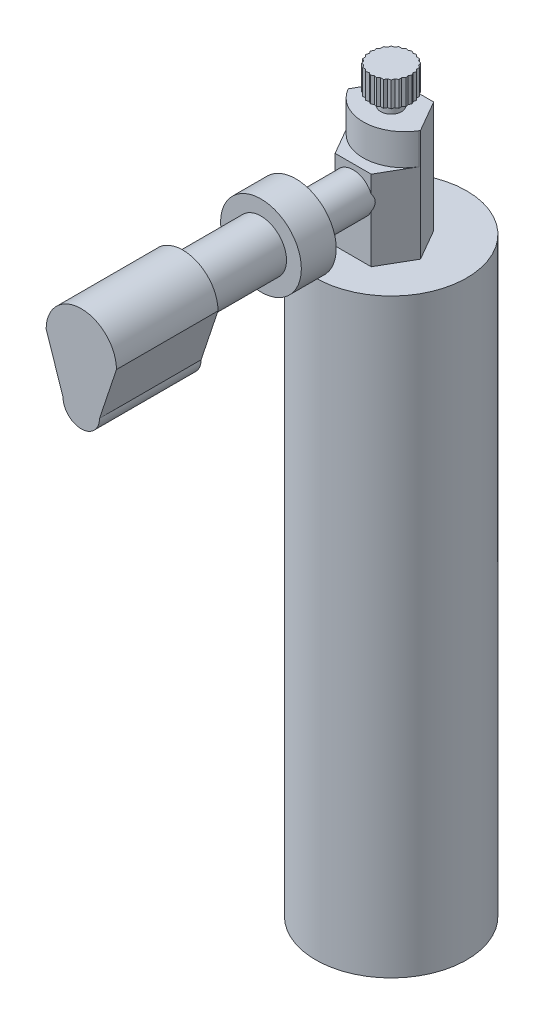
SolidWorks part; units mm, degrees
ref_plane "Front Plane" through (0, 0, 0) normal (0, 0, 1) x (1, 0, 0)
ref_plane "Top Plane" through (0, 0, 0) normal (0, 1, 0) x (1, 0, 0)
ref_plane "Right Plane" through (0, 0, 0) normal (1, 0, 0) x (0, 0, -1)
sketch "Sketch1" plane through (0, 0, 0) normal (0, 1, 0) x (1, 0, 0)
  circle A0 centre (0, 0) radius 14.5
  dimension "D1" = 29
extrude "Boss-Extrude1" add sketch "Sketch1" along normal blind 113.4
sketch "Sketch2" plane through (0, 113.4, 0) normal (0, 1, 0) x (1, 0, 0)
  circle A0 centre (0, 0) radius 2
  dimension "D1" = 4
extrude "Boss-Extrude2" add sketch "Sketch2" along normal blind 28.5
sketch "Sketch3" plane through (0, 141.9, 0) normal (0, 1, 0) x (1, 0, 0)
  circle A0 centre (0, 0) radius 4
  dimension "D1" = 8
extrude "Boss-Extrude3" add sketch "Sketch3" against normal blind 4.8
sketch "Sketch4" plane through (0, 113.4, 0) normal (0, 1, 0) x (1, 0, 0)
  line L3 (3.4641, 4.7) -> (-3.4641, 4.7)
  line L4 (-3.4641, 4.7) -> (-6.9282, -1.3)
  line L5 (-6.9282, -1.3) -> (-3.4641, -7.3)
  line L6 (-3.4641, -7.3) -> (3.4641, -7.3)
  line L7 (3.4641, -7.3) -> (6.9282, -1.3)
  line L8 (6.9282, -1.3) -> (3.4641, 4.7)
  circle A0 centre (0, 0) radius 14.5 construction
  circle A1 centre (0, -1.3) radius 6.9282 construction
  circle A4 centre (0, 0) radius 14.5 construction
  dimension "D1" = 12
  dimension "D2" = 4.7
extrude "Boss-Extrude4" add sketch "Sketch4" along normal blind 21.4
sketch "Sketch6" plane through (0, 134.8, 0) normal (0, 1, 0) x (1, 0, 0)
  line L4 (-6.9282, -1.3) -> (-6.9282, -9.4658)
  line L5 (-6.9282, -9.4658) -> (6.9282, -9.4658)
  line L6 (6.9282, -1.3) -> (6.9282, -9.4658)
  arc A0 (-6.9282, -1.3) -> (6.9282, -1.3) centre (0, 2.5618) ccw
extrude "Cut-Extrude1" cut sketch "Sketch6" against normal blind 6
sketch "Sketch7" plane through (0, 0, 7.3) normal (0, 0, 1) x (1, 0, 0)
  line L0 (-3.4641, 128.8) -> (3.4641, 128.8) construction
  circle A0 centre (0, 124.05) radius 3.75
  dimension "D1" = 7.5
  dimension "D2" = 4.75
extrude "Boss-Extrude5" add sketch "Sketch7" along normal blind 11 and the other way blind 2
sketch "Sketch8" plane through (0, 0, 18.3) normal (0, 0, 1) x (1, 0, 0)
  circle A0 centre (0, 124.05) radius 7.75
  dimension "D1" = 15.5
extrude "Boss-Extrude6" add sketch "Sketch8" along normal blind 6.7
sketch "Sketch9" plane through (0, 0, 25) normal (0, 0, 1) x (1, 0, 0)
  circle A0 centre (0, 124.05) radius 4.9
  dimension "D1" = 9.8
extrude "Boss-Extrude7" add sketch "Sketch9" along normal blind 15
sketch "Sketch10" plane through (0, 0, 40) normal (0, 0, 1) x (1, 0, 0)
  line L0 (0, 117.8) -> (0, 110.8) construction
  line L1 (-6.75, 124.05) -> (-3.5, 114.3)
  line L2 (3.5, 114.3) -> (6.75, 124.05)
  arc A0 (6.75, 124.05) -> (-6.75, 124.05) centre (0, 124.05) ccw
  arc A1 (-3.5, 114.3) -> (3.5, 114.3) centre (0, 114.3) ccw
  dimension "D1" = 13.5
  dimension "D2" = 7
extrude "Boss-Extrude8" add sketch "Sketch10" along normal blind 19.5
sketch "Sketch11" plane through (0, 141.9, 0) normal (0, 1, 0) x (1, 0, 0)
  line L0 (0, 4) -> (0.2732, 3.6147)
  line L1 (0, 4) -> (0, 3.625) construction
  line L2 (0, 4) -> (-0.2732, 3.6147)
  line L3 (0.6106, 3.9531) -> (0.8217, 3.5306)
  line L4 (0.6106, 3.9531) -> (0.2818, 3.614)
  line L5 (1.2069, 3.8136) -> (1.351, 3.3638)
  line L6 (1.2069, 3.8136) -> (0.8302, 3.5287)
  line L7 (1.7749, 3.5847) -> (1.8487, 3.1182)
  line L8 (1.7749, 3.5847) -> (1.3591, 3.3606)
  line L9 (2.3013, 3.2717) -> (2.303, 2.7994)
  line L10 (2.3013, 3.2717) -> (1.8562, 3.1137)
  line L11 (2.7737, 2.8821) -> (2.7034, 2.4151)
  line L12 (2.7737, 2.8821) -> (2.3097, 2.7939)
  line L13 (3.1812, 2.4249) -> (3.0403, 1.9741)
  line L14 (3.1812, 2.4249) -> (2.7091, 2.4086)
  line L15 (3.514, 1.9109) -> (3.306, 1.4868)
  line L16 (3.514, 1.9109) -> (3.0451, 1.9668)
  line L17 (3.7646, 1.3521) -> (3.4943, 0.9648)
  line L18 (3.7646, 1.3521) -> (3.3096, 1.4789)
  line L19 (3.9268, 0.7616) -> (3.6006, 0.4201)
  line L20 (3.9268, 0.7616) -> (3.4966, 0.9564)
  line L21 (3.9971, 0.1532) -> (3.6225, -0.1345)
  line L22 (3.9971, 0.1532) -> (3.6016, 0.4114)
  line L23 (3.9736, -0.4587) -> (3.5595, -0.6859)
  line L24 (3.9736, -0.4587) -> (3.6222, -0.1432)
  line L25 (3.857, -1.0599) -> (3.4131, -1.2212)
  line L26 (3.857, -1.0599) -> (3.5579, -0.6944)
  line L27 (3.65, -1.6363) -> (3.1867, -1.7279)
  line L28 (3.65, -1.6363) -> (3.4102, -1.2294)
  line L29 (3.3575, -2.1743) -> (2.8856, -2.1941)
  line L30 (3.3575, -2.1743) -> (3.1825, -1.7356)
  line L31 (2.9862, -2.6613) -> (2.5168, -2.6089)
  line L32 (2.9862, -2.6613) -> (2.8803, -2.201)
  line L33 (2.545, -3.086) -> (2.0891, -2.9625)
  line L34 (2.545, -3.086) -> (2.5106, -2.6149)
  line L35 (2.0441, -3.4383) -> (1.6124, -3.2467)
  line L36 (2.0441, -3.4383) -> (2.082, -2.9675)
  line L37 (1.4953, -3.71) -> (1.0979, -3.4547)
  line L38 (1.4953, -3.71) -> (1.6046, -3.2505)
  line L39 (0.9114, -3.8948) -> (0.5577, -3.5818)
  line L40 (0.9114, -3.8948) -> (1.0896, -3.4574)
  line L41 (0.3062, -3.9883) -> (0.0044, -3.625)
  line L42 (0.3062, -3.9883) -> (0.5491, -3.5832)
  line L43 (-0.3062, -3.9883) -> (-0.5491, -3.5832)
  line L44 (-0.3062, -3.9883) -> (-0.0044, -3.625)
  line L45 (-0.9114, -3.8948) -> (-1.0896, -3.4574)
  line L46 (-0.9114, -3.8948) -> (-0.5577, -3.5818)
  line L47 (-1.4953, -3.71) -> (-1.6046, -3.2505)
  line L48 (-1.4953, -3.71) -> (-1.0979, -3.4547)
  line L49 (-2.0441, -3.4383) -> (-2.082, -2.9675)
  line L50 (-2.0441, -3.4383) -> (-1.6124, -3.2467)
  line L51 (-2.545, -3.086) -> (-2.5106, -2.6149)
  line L52 (-2.545, -3.086) -> (-2.0891, -2.9625)
  line L53 (-2.9862, -2.6613) -> (-2.8803, -2.201)
  line L54 (-2.9862, -2.6613) -> (-2.5168, -2.6089)
  line L55 (-3.3575, -2.1743) -> (-3.1825, -1.7356)
  line L56 (-3.3575, -2.1743) -> (-2.8856, -2.1941)
  line L57 (-3.65, -1.6363) -> (-3.4102, -1.2294)
  line L58 (-3.65, -1.6363) -> (-3.1867, -1.7279)
  line L59 (-3.857, -1.0599) -> (-3.5579, -0.6944)
  line L60 (-3.857, -1.0599) -> (-3.4131, -1.2212)
  line L61 (-3.9736, -0.4587) -> (-3.6222, -0.1432)
  line L62 (-3.9736, -0.4587) -> (-3.5595, -0.6859)
  line L63 (-3.9971, 0.1532) -> (-3.6016, 0.4114)
  line L64 (-3.9971, 0.1532) -> (-3.6225, -0.1345)
  line L65 (-3.9268, 0.7616) -> (-3.4966, 0.9564)
  line L66 (-3.9268, 0.7616) -> (-3.6006, 0.4201)
  line L67 (-3.7646, 1.3521) -> (-3.3096, 1.4789)
  line L68 (-3.7646, 1.3521) -> (-3.4943, 0.9648)
  line L69 (-3.514, 1.9109) -> (-3.0451, 1.9668)
  line L70 (-3.514, 1.9109) -> (-3.306, 1.4868)
  line L71 (-3.1812, 2.4249) -> (-2.7091, 2.4086)
  line L72 (-3.1812, 2.4249) -> (-3.0403, 1.9741)
  line L73 (-2.7737, 2.8821) -> (-2.3097, 2.7939)
  line L74 (-2.7737, 2.8821) -> (-2.7034, 2.4151)
  line L75 (-2.3013, 3.2717) -> (-1.8562, 3.1137)
  line L76 (-2.3013, 3.2717) -> (-2.303, 2.7994)
  line L77 (-1.7749, 3.5847) -> (-1.3591, 3.3606)
  line L78 (-1.7749, 3.5847) -> (-1.8487, 3.1182)
  line L79 (-1.2069, 3.8136) -> (-0.8302, 3.5287)
  line L80 (-1.2069, 3.8136) -> (-1.351, 3.3638)
  line L81 (-0.6106, 3.9531) -> (-0.2818, 3.614)
  line L82 (-0.6106, 3.9531) -> (-0.8217, 3.5306)
  arc A0 (-0.2732, 3.6147) -> (-0.2818, 3.614) centre (0, 0) ccw construction
  circle A1 centre (0, 0) radius 4 construction
  circle A2 centre (0, 0) radius 4
  arc A3 (0.2818, 3.614) -> (0.2732, 3.6147) centre (0, 0) ccw
  arc A4 (0.2818, 3.614) -> (0.2732, 3.6147) centre (0, 0) ccw construction
  arc A5 (0.8302, 3.5287) -> (0.8217, 3.5306) centre (0, 0) ccw construction
  arc A6 (0.8302, 3.5287) -> (0.8217, 3.5306) centre (0, 0) ccw
  arc A7 (1.3591, 3.3606) -> (1.351, 3.3638) centre (0, 0) ccw construction
  arc A8 (1.3591, 3.3606) -> (1.351, 3.3638) centre (0, 0) ccw
  arc A9 (-0.2732, 3.6147) -> (-0.2818, 3.614) centre (0, 0) ccw
  arc A10 (-0.8217, 3.5306) -> (-0.8302, 3.5287) centre (0, 0) ccw construction
  arc A11 (-0.8217, 3.5306) -> (-0.8302, 3.5287) centre (0, 0) ccw
  arc A12 (-1.351, 3.3638) -> (-1.3591, 3.3606) centre (0, 0) ccw construction
  arc A13 (-1.351, 3.3638) -> (-1.3591, 3.3606) centre (0, 0) ccw
  arc A14 (-1.8487, 3.1182) -> (-1.8562, 3.1137) centre (0, 0) ccw construction
  arc A15 (-1.8487, 3.1182) -> (-1.8562, 3.1137) centre (0, 0) ccw
  arc A16 (1.8562, 3.1137) -> (1.8487, 3.1182) centre (0, 0) ccw construction
  arc A17 (1.8562, 3.1137) -> (1.8487, 3.1182) centre (0, 0) ccw
  arc A18 (2.3097, 2.7939) -> (2.303, 2.7994) centre (0, 0) ccw construction
  arc A19 (2.3097, 2.7939) -> (2.303, 2.7994) centre (0, 0) ccw
  arc A20 (2.7091, 2.4086) -> (2.7034, 2.4151) centre (0, 0) ccw construction
  arc A21 (2.7091, 2.4086) -> (2.7034, 2.4151) centre (0, 0) ccw
  arc A22 (3.0451, 1.9668) -> (3.0403, 1.9741) centre (0, 0) ccw construction
  arc A23 (3.0451, 1.9668) -> (3.0403, 1.9741) centre (0, 0) ccw
  arc A24 (3.3096, 1.4789) -> (3.306, 1.4868) centre (0, 0) ccw construction
  arc A25 (3.3096, 1.4789) -> (3.306, 1.4868) centre (0, 0) ccw
  arc A26 (3.4966, 0.9564) -> (3.4943, 0.9648) centre (0, 0) ccw construction
  arc A27 (3.4966, 0.9564) -> (3.4943, 0.9648) centre (0, 0) ccw
  arc A28 (3.6016, 0.4114) -> (3.6006, 0.4201) centre (0, 0) ccw construction
  arc A29 (3.6016, 0.4114) -> (3.6006, 0.4201) centre (0, 0) ccw
  arc A30 (3.6222, -0.1432) -> (3.6225, -0.1345) centre (0, 0) ccw construction
  arc A31 (3.6222, -0.1432) -> (3.6225, -0.1345) centre (0, 0) ccw
  arc A32 (3.5579, -0.6944) -> (3.5595, -0.6859) centre (0, 0) ccw construction
  arc A33 (3.5579, -0.6944) -> (3.5595, -0.6859) centre (0, 0) ccw
  arc A34 (3.4102, -1.2294) -> (3.4131, -1.2212) centre (0, 0) ccw construction
  arc A35 (3.4102, -1.2294) -> (3.4131, -1.2212) centre (0, 0) ccw
  arc A36 (3.1825, -1.7356) -> (3.1867, -1.7279) centre (0, 0) ccw construction
  arc A37 (3.1825, -1.7356) -> (3.1867, -1.7279) centre (0, 0) ccw
  arc A38 (2.8803, -2.201) -> (2.8856, -2.1941) centre (0, 0) ccw construction
  arc A39 (2.8803, -2.201) -> (2.8856, -2.1941) centre (0, 0) ccw
  arc A40 (2.5106, -2.6149) -> (2.5168, -2.6089) centre (0, 0) ccw construction
  arc A41 (2.5106, -2.6149) -> (2.5168, -2.6089) centre (0, 0) ccw
  arc A42 (2.082, -2.9675) -> (2.0891, -2.9625) centre (0, 0) ccw construction
  arc A43 (2.082, -2.9675) -> (2.0891, -2.9625) centre (0, 0) ccw
  arc A44 (1.6046, -3.2505) -> (1.6124, -3.2467) centre (0, 0) ccw construction
  arc A45 (1.6046, -3.2505) -> (1.6124, -3.2467) centre (0, 0) ccw
  arc A46 (1.0896, -3.4574) -> (1.0979, -3.4547) centre (0, 0) ccw construction
  arc A47 (1.0896, -3.4574) -> (1.0979, -3.4547) centre (0, 0) ccw
  arc A48 (0.5491, -3.5832) -> (0.5577, -3.5818) centre (0, 0) ccw construction
  arc A49 (0.5491, -3.5832) -> (0.5577, -3.5818) centre (0, 0) ccw
  arc A50 (-0.0044, -3.625) -> (0.0044, -3.625) centre (0, 0) ccw construction
  arc A51 (-0.5577, -3.5818) -> (-0.5491, -3.5832) centre (0, 0) ccw construction
  arc A52 (-0.5577, -3.5818) -> (-0.5491, -3.5832) centre (0, 0) ccw
  arc A53 (-0.0044, -3.625) -> (0.0044, -3.625) centre (0, 0) ccw
  arc A54 (-1.0979, -3.4547) -> (-1.0896, -3.4574) centre (0, 0) ccw construction
  arc A55 (-1.0979, -3.4547) -> (-1.0896, -3.4574) centre (0, 0) ccw
  arc A56 (-1.6124, -3.2467) -> (-1.6046, -3.2505) centre (0, 0) ccw construction
  arc A57 (-1.6124, -3.2467) -> (-1.6046, -3.2505) centre (0, 0) ccw
  arc A58 (-2.0891, -2.9625) -> (-2.082, -2.9675) centre (0, 0) ccw construction
  arc A59 (-2.0891, -2.9625) -> (-2.082, -2.9675) centre (0, 0) ccw
  arc A60 (-2.5168, -2.6089) -> (-2.5106, -2.6149) centre (0, 0) ccw construction
  arc A61 (-2.5168, -2.6089) -> (-2.5106, -2.6149) centre (0, 0) ccw
  arc A62 (-2.8856, -2.1941) -> (-2.8803, -2.201) centre (0, 0) ccw construction
  arc A63 (-2.8856, -2.1941) -> (-2.8803, -2.201) centre (0, 0) ccw
  arc A64 (-3.1867, -1.7279) -> (-3.1825, -1.7356) centre (0, 0) ccw construction
  arc A65 (-3.1867, -1.7279) -> (-3.1825, -1.7356) centre (0, 0) ccw
  arc A66 (-3.4131, -1.2212) -> (-3.4102, -1.2294) centre (0, 0) ccw construction
  arc A67 (-3.4131, -1.2212) -> (-3.4102, -1.2294) centre (0, 0) ccw
  arc A68 (-3.5595, -0.6859) -> (-3.5579, -0.6944) centre (0, 0) ccw construction
  arc A69 (-3.5595, -0.6859) -> (-3.5579, -0.6944) centre (0, 0) ccw
  arc A70 (-3.6225, -0.1345) -> (-3.6222, -0.1432) centre (0, 0) ccw construction
  arc A71 (-3.6225, -0.1345) -> (-3.6222, -0.1432) centre (0, 0) ccw
  arc A72 (-3.6006, 0.4201) -> (-3.6016, 0.4114) centre (0, 0) ccw construction
  arc A73 (-3.6006, 0.4201) -> (-3.6016, 0.4114) centre (0, 0) ccw
  arc A74 (-3.4943, 0.9648) -> (-3.4966, 0.9564) centre (0, 0) ccw construction
  arc A75 (-3.4943, 0.9648) -> (-3.4966, 0.9564) centre (0, 0) ccw
  arc A76 (-3.306, 1.4868) -> (-3.3096, 1.4789) centre (0, 0) ccw construction
  arc A77 (-3.0403, 1.9741) -> (-3.0451, 1.9668) centre (0, 0) ccw construction
  arc A78 (-3.0403, 1.9741) -> (-3.0451, 1.9668) centre (0, 0) ccw
  arc A79 (-2.7034, 2.4151) -> (-2.7091, 2.4086) centre (0, 0) ccw construction
  arc A80 (-2.7034, 2.4151) -> (-2.7091, 2.4086) centre (0, 0) ccw
  arc A81 (-2.303, 2.7994) -> (-2.3097, 2.7939) centre (0, 0) ccw construction
  arc A82 (-2.303, 2.7994) -> (-2.3097, 2.7939) centre (0, 0) ccw
  arc A83 (-3.306, 1.4868) -> (-3.3096, 1.4789) centre (0, 0) ccw
  point P132 (0, 0)
  circle M1 centre (0, 0) radius 4
  dimension "D1" = 7.25
  dimension "D2" = 41
extrude "Cut-Extrude2" [suppressed] cut sketch "Sketch11" against normal up to surface (4.8 mm away) contours A3 L4 L0 M1 | A6 L6 L3 M1 | A8 L8 L5 M1 | A17 L10 L7 M1 | A19 L12 L9 M1 | A21 L14 L11 M1 | A23 L16 L13 M1 | A25 L18 L15 M1 | A27 L20 L17 M1 | A29 L22 L19 M1 | A31 L24 L21 M1 | A33 L26 L23 M1 | A35 L28 L25 M1 | A37 L30 L27 M1 | A39 L32 L29 M1 | A43 L36 L33 M1 | A41 L34 L31 M1 | A45 L38 L35 M1 | A47 L40 L37 M1 | A49 L42 L39 M1 | A53 L44 L41 M1 | A52 L46 L43 M1 | A55 L48 L45 M1 | A57 L50 L47 M1 | A59 L52 L49 M1 | A61 L54 L51 M1 | A63 L56 L53 M1 | A65 L58 L55 M1 | A67 L60 L57 M1 | A69 L62 L59 M1 | A71 L64 L61 M1 | A73 L66 L63 M1 | A75 L68 L65 M1 | A83 L70 L67 M1 | A78 L72 L69 M1 | A80 L74 L71 M1 | A9 L2 L81 M1 | A11 L82 L79 M1 | A13 L80 L77 M1 | A15 L78 L75 M1 | A82 L76 L73 M1 up to face at (0, 137.1, 4)
sketch "Sketch13" plane through (0, 141.9, 0) normal (0, 1, 0) x (1, 0, 0)
  line L0 (1.0353, 3.8637) -> (1.4351, 3.4645)
  line L1 (1.4351, 3.4645) -> (2, 3.4641)
  line L2 (2, 3.4641) -> (2.2829, 2.9751)
  line L3 (2.2829, 2.9751) -> (2.8284, 2.8284)
  line L4 (2.8284, 2.8284) -> (2.9751, 2.2829)
  line L5 (2.9751, 2.2829) -> (3.4641, 2)
  line L6 (3.4641, 2) -> (3.4645, 1.4351)
  line L7 (3.4645, 1.4351) -> (3.8637, 1.0353)
  line L8 (3.8637, 1.0353) -> (3.7179, 0.4895)
  line L9 (3.7179, 0.4895) -> (4, 0)
  line L10 (4, 0) -> (3.7179, -0.4895)
  line L11 (3.7179, -0.4895) -> (3.8637, -1.0353)
  line L12 (3.8637, -1.0353) -> (3.4645, -1.4351)
  line L13 (3.4645, -1.4351) -> (3.4641, -2)
  line L14 (3.4641, -2) -> (2.9751, -2.2829)
  line L15 (2.9751, -2.2829) -> (2.8284, -2.8284)
  line L16 (2.8284, -2.8284) -> (2.2829, -2.9751)
  line L17 (2.2829, -2.9751) -> (2, -3.4641)
  line L18 (2, -3.4641) -> (1.4351, -3.4645)
  line L19 (1.4351, -3.4645) -> (1.0353, -3.8637)
  line L20 (1.0353, -3.8637) -> (0.4895, -3.7179)
  line L21 (0.4895, -3.7179) -> (0, -4)
  line L22 (0, -4) -> (-0.4895, -3.7179)
  line L23 (-0.4895, -3.7179) -> (-1.0353, -3.8637)
  line L24 (-1.0353, -3.8637) -> (-1.4351, -3.4645)
  line L25 (-1.4351, -3.4645) -> (-2, -3.4641)
  line L26 (0, 4) -> (0.4895, 3.7179)
  line L27 (0.4895, 3.7179) -> (1.0353, 3.8637)
  line L28 (-2, -3.4641) -> (-2.2829, -2.9751)
  line L29 (-2.2829, -2.9751) -> (-2.8284, -2.8284)
  line L30 (-2.8284, -2.8284) -> (-2.9751, -2.2829)
  line L31 (-2.9751, -2.2829) -> (-3.4641, -2)
  line L32 (-3.4641, -2) -> (-3.4645, -1.4351)
  line L33 (-3.4645, -1.4351) -> (-3.8637, -1.0353)
  line L34 (-3.8637, -1.0353) -> (-3.7179, -0.4895)
  line L35 (-3.7179, -0.4895) -> (-4, 0)
  line L36 (-4, 0) -> (-3.7179, 0.4895)
  line L37 (-3.7179, 0.4895) -> (-3.8637, 1.0353)
  line L38 (-3.8637, 1.0353) -> (-3.4645, 1.4351)
  line L39 (-3.4645, 1.4351) -> (-3.4641, 2)
  line L40 (-3.4641, 2) -> (-2.9751, 2.2829)
  line L41 (-2.9751, 2.2829) -> (-2.8284, 2.8284)
  line L42 (-2.8284, 2.8284) -> (-2.2829, 2.9751)
  line L43 (-2.2829, 2.9751) -> (-2, 3.4641)
  line L44 (-2, 3.4641) -> (-1.4351, 3.4645)
  line L45 (-1.4351, 3.4645) -> (-1.0353, 3.8637)
  line L46 (-1.0353, 3.8637) -> (-0.4895, 3.7179)
  line L47 (-0.4895, 3.7179) -> (0, 4)
  circle A1 centre (0, 0) radius 4 construction
  point P10 (0, 0)
  point P14 (0, 0)
  point P18 (0, 0)
  point P22 (0, 0)
  point P26 (0, 0)
  point P30 (0, 0)
  point P32 (0, 0)
  point P36 (0, 0)
  point P40 (0, 0)
  point P44 (0, 0)
  point P48 (0, 0)
  point P52 (0, 0)
  point P56 (0, 0)
  point P60 (0, 0)
  point P64 (0, 0)
  point P68 (0, 0)
  point P72 (0, 0)
  point P76 (0, 0)
  point P80 (0, 0)
  point P84 (0, 0)
  point P88 (0, 0)
  point P92 (0, 0)
  point P96 (0, 0)
  point P100 (0, 0)
  point P102 (0, 0)
  dimension "D1" = 24
extrude "Cut-Extrude3" cut sketch "Sketch13" against normal blind 6 flip side to cut
